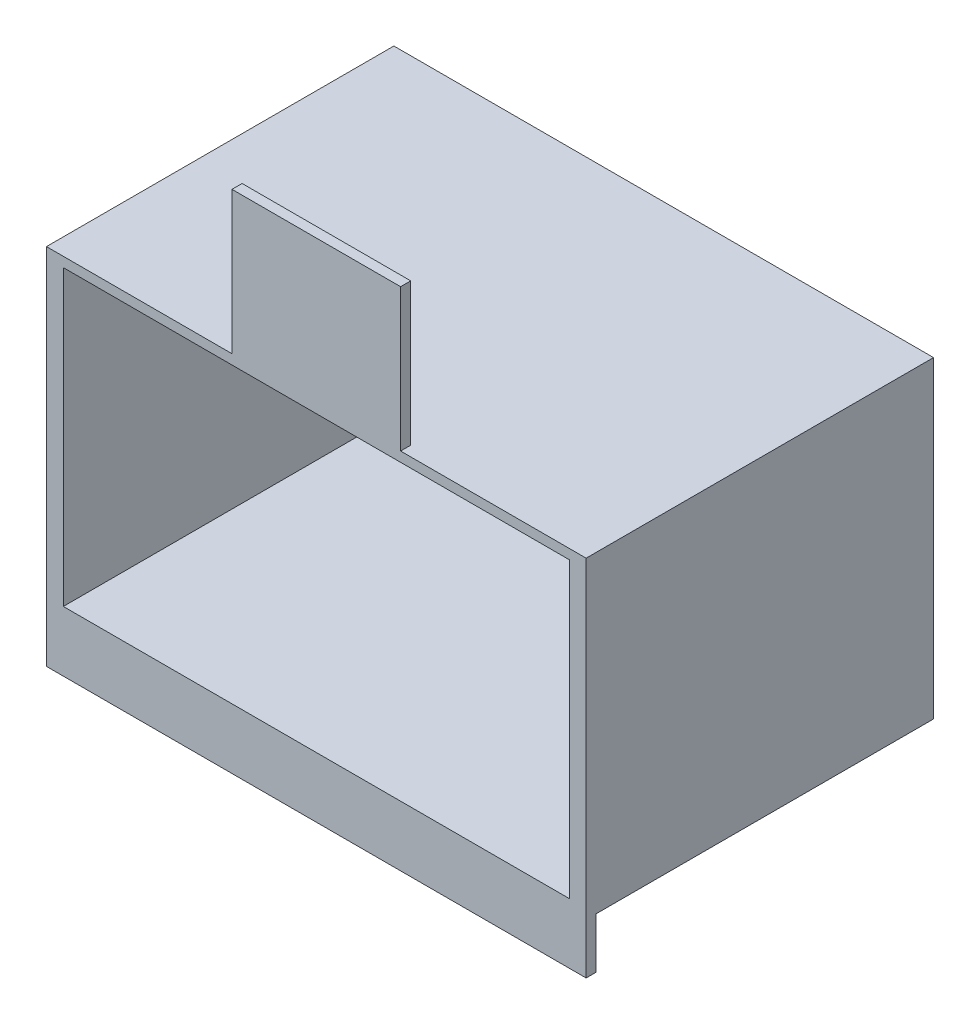
SolidWorks part; units mm, degrees
ref_plane "Front Plane" through (0, 0, 0) normal (0, 0, 1) x (1, 0, 0)
ref_plane "Top Plane" through (0, 0, 0) normal (0, 1, 0) x (1, 0, 0)
ref_plane "Right Plane" through (0, 0, 0) normal (1, 0, 0) x (0, 0, -1)
sketch "ｽｹｯﾁ1" plane through (0, 0, 0) normal (0, 0, 1) x (1, 0, 0)
  line L1 (-80, 75) -> (80, 75)
  line L2 (-80, 75) -> (-80, -75)
  line L3 (-80, -75) -> (80, -75)
  line L4 (80, 75) -> (80, -75)
  line L5 (-80, 75) -> (80, -75) construction
  line L6 (-80, -75) -> (80, 75) construction
  point P0 (0, 0)
  dimension "D1" = 160
  dimension "D2" = 150
extrude "ﾎﾞｽ - 押し出し1" add sketch "ｽｹｯﾁ1" along normal blind 3
sketch "ｽｹｯﾁ2" plane through (0, 0, 3) normal (0, 0, 1) x (1, 0, 0)
  line L0 (-80, -75) -> (80, -75) construction
  line L1 (-80, 32.8) -> (80, 32.8)
  line L2 (-80, 32.8) -> (-80, -60)
  line L3 (-80, -60) -> (80, -60)
  line L4 (80, 32.8) -> (80, -60)
  line L5 (-80, 32.8) -> (80, -60) construction
  line L6 (-80, -60) -> (80, 32.8) construction
  line L7 (-75, 29.9) -> (75, 29.9)
  line L8 (-75, 29.9) -> (-75, -57.1)
  line L9 (-75, -57.1) -> (75, -57.1)
  line L10 (75, 29.9) -> (75, -57.1)
  line L11 (-75, 29.9) -> (75, -57.1) construction
  line L12 (-75, -57.1) -> (75, 29.9) construction
  line L14 (0, 0) -> (0, -60) construction
  point P5 (0, 0)
  point P7 (0, -57.1)
  dimension "D1" = 160
  dimension "D2" = 150
  dimension "D3" = 87
  dimension "D4" = 15
extrude "ﾎﾞｽ - 押し出し2" add sketch "ｽｹｯﾁ2" along normal blind 100
sketch "ｽｹｯﾁ4" plane through (0, 0, 3) normal (0, 0, 1) x (1, 0, 0)
  line L0 (0, -1.65) -> (0, 1.65) construction
  line L1 (-80, 75) -> (-25, 75)
  line L2 (-80, 75) -> (-80, 32.8)
  line L3 (-80, 32.8) -> (-25, 32.8)
  line L4 (-25, 75) -> (-25, 32.8)
  line L5 (80, 75) -> (25, 75)
  line L6 (80, 75) -> (80, 32.8)
  line L7 (80, 32.8) -> (25, 32.8)
  line L8 (25, 75) -> (25, 32.8)
  line L9 (80, 32.8) -> (-80, 32.8) construction
  dimension "D1" = 55
extrude "ｶｯﾄ - 押し出し2" cut sketch "ｽｹｯﾁ4" against normal blind 3
ref_plane "平面1" through (0, 0, 100) normal (0, 0, -1) x (-1, 0, 0)
sketch "ｽｹｯﾁ5" plane through (0, 0, 100) normal (0, 0, -1) x (-1, 0, 0)
  line L0 (-80, -60) -> (80, -60) construction
  line L1 (80, -60) -> (80, -75) construction
  line L2 (80, -75) -> (-80, -75) construction
  line L3 (-80, -75) -> (-80, -60) construction
  line L4 (25, 75) -> (25, 32.8) construction
  line L5 (25, 32.8) -> (-25, 32.8) construction
  line L6 (-25, 32.8) -> (-25, 75) construction
  line L7 (-25, 75) -> (25, 75) construction
  line L8 (-80, -60) -> (80, -60)
  line L9 (80, -60) -> (80, -75)
  line L10 (80, -75) -> (-80, -75)
  line L11 (-80, -75) -> (-80, -60)
  line L12 (25, 75) -> (25, 32.8)
  line L13 (25, 32.8) -> (-25, 32.8)
  line L14 (-25, 32.8) -> (-25, 75)
  line L15 (-25, 75) -> (25, 75)
extrude "ﾎﾞｽ - 押し出し3" add sketch "ｽｹｯﾁ5" against normal blind 3
extrude "ｶｯﾄ - 押し出し3" cut sketch "ｽｹｯﾁ5<2>" along normal through all
sketch "ｽｹｯﾁ5<2>" plane through (0, 0, 100) normal (0, 0, -1) x (-1, 0, 0) same geometry as "ｽｹｯﾁ5"
